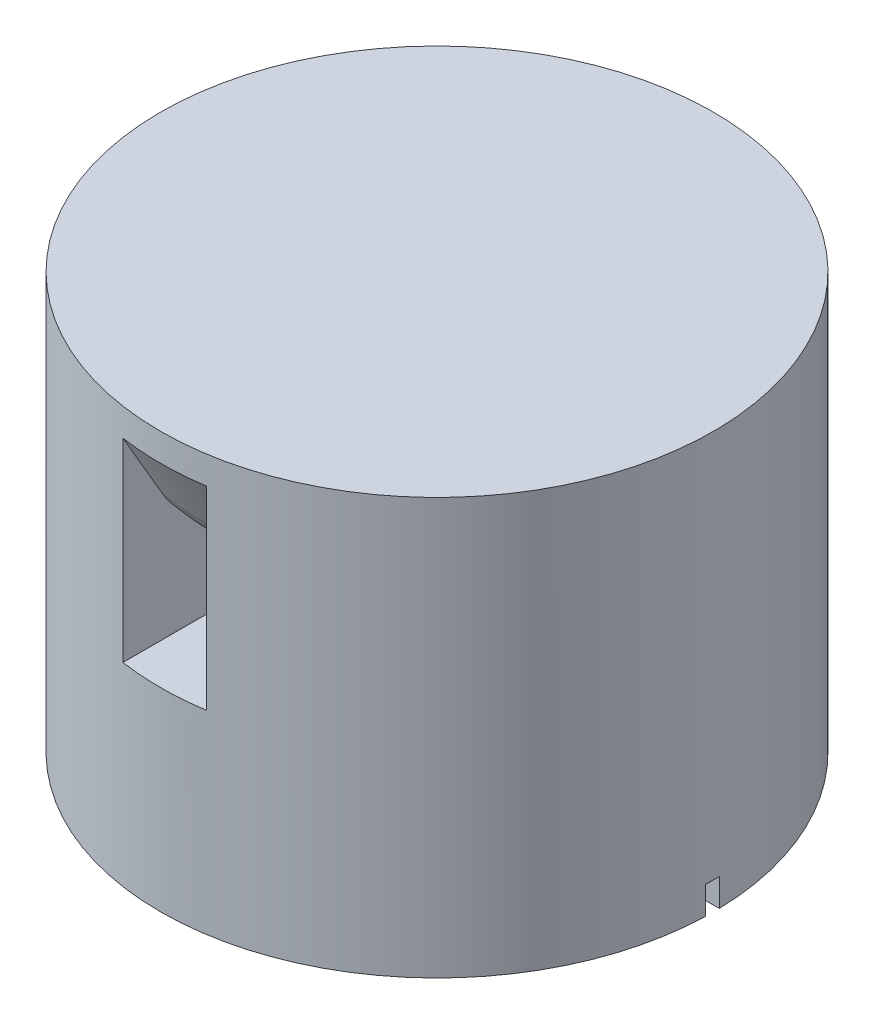
SolidWorks part; units mm, degrees
ref_plane "Front Plane" through (0, 0, 0) normal (0, 0, 1) x (1, 0, 0)
ref_plane "Top Plane" through (0, 0, 0) normal (0, 1, 0) x (1, 0, 0)
ref_plane "Right Plane" through (0, 0, 0) normal (1, 0, 0) x (0, 0, -1)
sketch "Sketch4" plane through (0, 0, 0) normal (0, 1, 0) x (1, 0, 0)
  circle A0 centre (-20.5796, -33.8554) radius 12.6543
extrude "Boss-Extrude3" add sketch "Sketch4" along normal blind 19.05
sketch "Sketch5" plane through (0, 19.05, 0) normal (0, 1, 0) x (1, 0, 0)
  line L0 (-10.0887, -40.9316) -> (-20.5796, -33.8554)
  line L1 (-20.5796, -33.8554) -> (-20.5796, -46.5097)
  circle A1 centre (-20.5796, -33.8554) radius 12.6543 construction
  dimension "D1" = 12.6543
  dimension "D2" = 12.6543
  dimension "D3" = 56
ref_plane "Plane6" through (0, 0, 46.5097) normal (0, 0, 1) x (1, 0, 0)
sketch "Sketch6" plane through (0, 0, 46.5097) normal (0, 0, 1) x (1, 0, 0)
  line L1 (-22.4389, 12.7) -> (-18.6289, 12.7)
  line L2 (-22.4389, 12.7) -> (-22.4389, 8.89)
  line L3 (-22.4389, 8.89) -> (-18.6289, 8.89)
  line L4 (-18.6289, 12.7) -> (-18.6289, 8.89)
  line L7 (-7.9253, 19.05) -> (-33.2339, 19.05) construction
  dimension "D1" = 3.81
  dimension "D4" = 6.35
sketch "Sketch8" plane through (0, 19.05, 0) normal (0, 1, 0) x (1, 0, 0)
  line L0 (-20.5796, -33.8554) -> (-33.2339, -33.8554)
  line L1 (-33.2339, -33.8554) -> (-7.9253, -33.8554)
  circle A0 centre (-20.5796, -33.8554) radius 12.6543 construction
extrude "Cut-Extrude5" cut sketch "Sketch6" against normal blind 5.08 contours L1 L4 L3 L2
chamfer "Chamfer4" distance 5.08 angle 30 1 edges at (-20.5334, 12.7, 46.5096) first distance on face at (-20.5796, 0, 46.5097)
fillet "Fillet1" radius 3.81 1 edges at (-20.533, 12.7, 43.5766)
pattern_circular "CirPattern1" count 2 over 360 about axis through (-20.5796, 19.05, 33.8554) along (0, -1, 0) of "Cut-Extrude5"
chamfer "Chamfer5" distance 5.08 angle 30 1 edges at (-20.6258, 12.7, 21.2011) first distance on face at (-20.5337, 13.335, 46.4375)
fillet "Fillet2" radius 3.81 1 edges at (-20.6262, 12.7, 24.1341)
sketch "Sketch10" plane through (0, 0, 0) normal (0, -1, 0) x (-1, 0, 0)
  line L1 (33.6612, -34.2213) -> (7.0309, -34.2213)
  line L2 (33.6612, -34.2213) -> (33.6612, -33.5863)
  line L3 (33.6612, -33.5863) -> (7.0309, -33.5863)
  line L4 (7.0309, -34.2213) -> (7.0309, -33.5863)
  line L5 (20.3461, -33.5863) -> (20.3461, -34.2213) construction
  line L6 (33.6612, -33.9038) -> (7.0309, -33.9038) construction
  dimension "D1" = 0.635
extrude "Cut-Extrude6" cut sketch "Sketch10" against normal blind 1.27
scale "Scale2" scale about centroid uniform scaling yes scale factor 0.5
